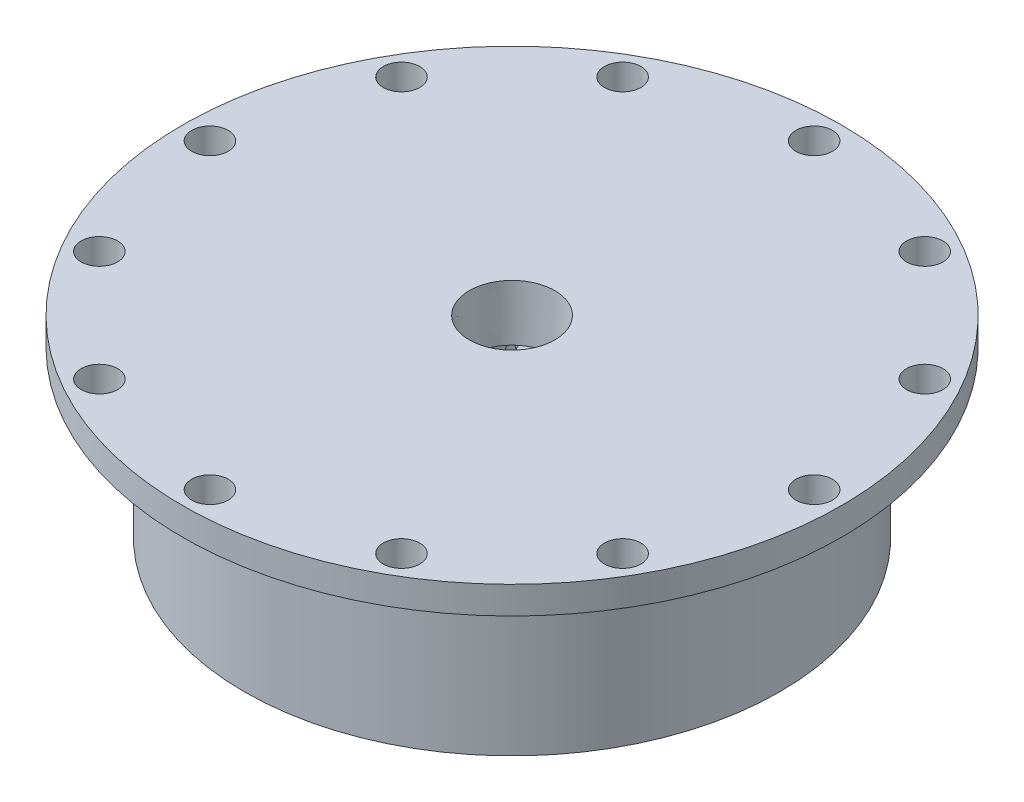
SolidWorks part; units mm, degrees
note: '?' marks a value the reader was unsure of.
ref_plane "Front Plane" through (0, 0, 0) normal (0, 0, 1) x (1, 0, 0)
ref_plane "Top Plane" through (0, 0, 0) normal (0, 1, 0) x (1, 0, 0)
ref_plane "Right Plane" through (0, 0, 0) normal (1, 0, 0) x (0, 0, -1)
sketch "Sketch1" plane through (0, 0, 0) normal (0, 0, 1) x (1, 0, 0)
  line L0 (0, 0) -> (-76.2, 0)
  line L1 (-76.2, 0) -> (-76.2, -6.35)
  line L2 (-76.2, -6.35) -> (-61.9125, -6.35)
  line L3 (-61.9125, -6.35) -> (-61.9125, -44.45)
  line L4 (-61.9125, -44.45) -> (-60.325, -44.45)
  line L5 (-46.0375, -34.925) -> (-46.0375, -50.8)
  line L6 (-46.0375, -50.8) -> (0, -50.8)
  line L7 (0, -50.8) -> (0, 0)
  line L8 (-46.0375, -44.45) -> (-55.5625, -44.45) construction
  line L9 (-60.325, -44.45) -> (-60.325, -42.418)
  line L10 (-60.325, -42.418) -> (-57.277, -42.418)
  line L11 (-57.277, -42.418) -> (-57.277, -44.45)
  line L12 (-57.277, -44.45) -> (-55.5625, -44.45)
  arc A0 (-55.5625, -44.45) -> (-46.0375, -34.925) centre (-46.0375, -44.45) cw
  dimension "D1" = 6.35
  dimension "D2" = 6.35
  dimension "D3" = 9.525
  dimension "D4" = 46.0375
  dimension "D5" = 38.1
  dimension "D6" = 76.2
  dimension "D7" = 6.35
  dimension "D8" = 3.048
  dimension "D9" = 1.5875
  dimension "D10" = 2.032
revolve "Revolve1" add sketch "Sketch1" angle 360 about L7
ref_axis "Axis2" through (0, 1.1112, 0) along (0, -1, 0)
ref_axis "Axis1" through (-83.82, 0, 0) along (1, 0, 0)?
sketch "Sketch2" plane through (0, 0, 0) normal (0, 0, 1) x (1, 0, 0)
  line L0 (0, -50.8) -> (-4.7625, -50.8)
  line L1 (-46.0375, -50.8) -> (46.0375, -50.8) construction
  line L2 (-4.7625, -49.2125) -> (-4.7625, -46.0375)
  line L3 (-4.7625, -46.0375) -> (-6.35, -44.45)
  line L4 (-6.35, -44.45) -> (-6.35, -31.75)
  line L5 (-6.35, -31.75) -> (0, -31.75)
  line L6 (0, -31.75) -> (0, -50.8)
  line L7 (-5.5562, -49.2125) -> (-5.5562, -46.7423)
  line L8 (-5.5562, -46.7423) -> (-7.1437, -45.1548)
  line L9 (-7.1437, -45.1548) -> (-7.1437, -38.1)
  line L10 (-7.1437, -38.1) -> (-10.3187, -38.1)
  line L11 (-10.3187, -38.1) -> (-10.3187, -43.6563)
  line L12 (-10.3187, -43.6563) -> (-6.35, -47.625)
  line L13 (-6.35, -47.625) -> (-6.35, -50.8)
  line L14 (-6.35, -50.8) -> (-5.5562, -50.8)
  line L15 (-5.5562, -49.2125) -> (-4.7625, -49.2125)
  line L16 (-5.5562, -50.8) -> (-4.7625, -50.8)
  line L17 (-4.7625, -50.8) -> (-4.7625, -49.2125) construction
  line L18 (-5.5562, -50.8) -> (-5.5562, -49.2125) construction
  dimension "D1" = 135
  dimension "D2" = 4.7625
  dimension "D3" = 0.7937
  dimension "D4" = 0.7937
  dimension "D5" = 135
  dimension "D6" = 1.5875
  dimension "D7" = 4.7625
  dimension "D8" = 1.5875
  dimension "D9" = 3.175
  dimension "D10" = 6.35
  dimension "D11" = 19.05
  dimension "D12" = 3.175
  dimension "D13" = 0.7937
revolve "Cut-Revolve1" cut sketch "Sketch2" angle 360 about L6
sketch "Sketch4" plane through (0, 0, 0) normal (0, 0, 1) x (1, 0, 0)
  line L0 (-7.9375, -30.1625) -> (-7.9375, -36.5125)
  line L1 (-7.9375, -36.5125) -> (-14.2875, -30.1625)
  line L2 (-7.9375, -30.1625) -> (-0.7938, -23.0187)
  line L3 (-14.2875, -30.1625) -> (-14.2875, -12.7)
  line L4 (-14.2875, -12.7) -> (-0.7937, -12.7)
  line L5 (-0.7938, -23.0187) -> (-0.7937, -12.7)
  line L7 (-6.35, -44.45) -> (-6.35, -31.75) construction
  line L8 (0, 1.1112) -> (0, -23.3363) construction
  line L10 (-7.1437, -38.1) -> (-10.3187, -38.1) construction
  line L11 (-6.35, -31.75) -> (0, -31.75) construction
  line L12 (-83.82, 0) -> (83.82, 0) construction
  dimension "D1" = 45
  dimension "D2" = 1.5875
  dimension "D3" = 14.2875
  dimension "D4" = 1.5875
  dimension "D5" = 0.7937
  dimension "D6" = 1.5875
  dimension "D7" = 12.7
revolve "Cut-Revolve2" cut sketch "Sketch4" angle 360 about axis through (0, 1.1112, 0) along (0, -1, 0)
pattern_linear "LPattern1" count 2 spacing 31.75 along (1, 0, 0) of "Cut-Revolve1", "Cut-Revolve2"
pattern_circular "CirPattern1" count 6 over 360 about axis through (0, 0, 0) along (0, 1, 0) of "LPattern1"
ref_plane "Plane7" through (0, 0, 0) normal (1, 0, 0) x (0, -1, 0)
sketch "Sketch15" plane through (0, 0, 0) normal (1, 0, 0) x (0, -1, 0)
  line L0 (-1.1112, 0) -> (23.3363, 0) construction
  line L1 (20.8301, 3.3676) -> (24.1977, 0)
  line L2 (24.1977, 0) -> (20.8301, -3.3676)
  arc A0 (20.8301, 3.3676) -> (20.8301, -3.3676) centre (17.4625, 0) ccw
  point P7 (12.7, 0)
  dimension "D1" = 4.7625
  dimension "D2" = 12.7
extrude "Cut-Extrude7" cut sketch "Sketch15" against normal blind 19.05 contours A0 L2 L1
pattern_circular "CirPattern11" count 6 over 360 about axis through (0, 0, 0) along (0, 1, 0) of "Cut-Extrude7"
ref_plane "Plane3" through (0, 0, 0) normal (0, 0, 1) x (0, -1, 0)
sketch "Sketch6" plane through (0, 0, 0) normal (0, 0, 1) x (0, -1, 0)
  line L0 (35.2538, 5.5563) -> (34.6925, 6.1175)
  line L1 (34.6925, 4.995) -> (35.2538, 5.5563)
  line L2 (34.1313, 5.5563) -> (35.2538, 5.5563) construction
  line L3 (34.1313, 5.5563) -> (34.1313, 6.35) construction
  line L4 (34.1313, 5.5563) -> (33.3375, 5.5563) construction
  line L5 (50.8, -4.7625) -> (50.8, 4.7625) construction
  arc A0 (34.6925, 6.1175) -> (34.6925, 4.995) centre (34.1313, 5.5563) ccw
  point P21 (50.8, 0)
  dimension "D2" = 0.7937
  dimension "D1" = 90
  dimension "D3" = 17.4625
  dimension "D4" = 6.35
extrude "Cut-Extrude3" cut sketch "Sketch6" against normal up to surface (5.0577 mm away)
ref_plane "Plane4" through (0, 0, 0) normal (-0.5, 0, 0.866) x (0, -1, 0)
sketch "Sketch7" plane through (0, 0, 0) normal (-0.5, 0, 0.866) x (0, -1, 0)
  line L0 (40.0163, 9.525) -> (39.455, 10.0863)
  line L1 (39.455, 8.9637) -> (40.0163, 9.525)
  line L2 (40.0163, 9.525) -> (38.8938, 9.525) construction
  line L3 (38.8938, 9.525) -> (38.8938, 8.7313) construction
  line L4 (38.8938, 9.525) -> (38.1, 9.525) construction
  line L5 (50.8, -4.7625) -> (50.8, 4.7625) construction
  line L6 (38.8938, 9.525) -> (38.8938, 10.3187) construction
  arc A0 (39.455, 10.0863) -> (39.455, 8.9637) centre (38.8938, 9.525) ccw
  point P6 (50.8, 0)
  dimension "D2" = 0.7937
  dimension "D1" = 90
  dimension "D3" = 10.3187
  dimension "D4" = 12.7
extrude "Cut-Extrude4" cut sketch "Sketch7" against normal blind 19.05
pattern_circular "CirPattern3" count 3 over 360 about axis through (0, 0, 0) along (0, 1, 0) of "Cut-Extrude3", "Cut-Extrude4"
ref_axis "Axis3" through (31.75, -44.45, 0) along (0, 1, 0)?
ref_plane "Plane5" through (0, 0, 0) normal (0, 0, 1) x (0, 1, 0)
sketch "Sketch8" plane through (0, 0, 0) normal (0, 0, 1) x (0, 1, 0)
  line L0 (-35.2538, -37.3062) -> (-34.6925, -37.8675)
  line L1 (-34.6925, -36.745) -> (-35.2538, -37.3062)
  line L2 (-34.1313, -37.3062) -> (-35.2538, -37.3062) construction
  line L3 (-34.1313, -37.3062) -> (-34.1313, -38.1) construction
  line L4 (-34.1313, -37.3062) -> (-33.3375, -37.3063) construction
  line L5 (-50.8, -26.9875) -> (-50.8, -36.5125) construction
  arc A0 (-34.6925, -37.8675) -> (-34.6925, -36.745) centre (-34.1313, -37.3062) ccw
  point P14 (-50.8, -31.75)
  dimension "D2" = 0.7937
  dimension "D1" = 90
  dimension "D3" = 6.35
  dimension "D4" = 17.4625
extrude "Cut-Extrude5" cut sketch "Sketch8" against normal blind 7.62
ref_plane "Plane6" through (23.8125, 0, -13.7482) normal (-0.866, 0, 0.5) x (0, 1, 0)
sketch "Sketch9" plane through (23.8125, 0, -13.7482) normal (-0.866, 0, 0.5) x (0, 1, 0)
  line L0 (-40.0163, -25.4) -> (-39.455, -25.9613)
  line L1 (-39.455, -24.8387) -> (-40.0163, -25.4)
  line L2 (-40.0163, -25.4) -> (-38.8938, -25.4) construction
  line L4 (-38.8938, -25.4) -> (-38.1, -25.4) construction
  line L5 (-50.8, -11.1125) -> (-50.8, -20.6375) construction
  line L6 (-38.8938, -25.4) -> (-38.8938, -26.1938) construction
  arc A0 (-39.455, -25.9613) -> (-39.455, -24.8387) centre (-38.8938, -25.4) ccw
  point P6 (-50.8, -15.875)
  dimension "D2" = 0.7937
  dimension "D1" = 90
  dimension "D3" = 10.3187
  dimension "D4" = 12.7
extrude "Cut-Extrude6" cut sketch "Sketch9" against normal blind 15.24
pattern_circular "CirPattern4" count 3 over 360 about axis through (31.75, 0, 0) along (0, 1, 0) of "Cut-Extrude5", "Cut-Extrude6"
pattern_circular "CirPattern9" count 6 over 360 about axis through (0, 0, 0) along (0, 1, 0) of "CirPattern4", "Cut-Extrude5", "Cut-Extrude6"
ref_plane "Plane2" through (-39.8696, 0, 23.0187) normal (-0.866, 0, 0.5) x (0, -1, 0)
sketch "Sketch5" plane through (-39.8696, 0, 23.0187) normal (-0.866, 0, 0.5) x (0, -1, 0)
  line L0 (42.2049, -2.2451) -> (44.45, 0)
  line L1 (44.45, 0) -> (42.2049, 2.2451)
  line L2 (39.9599, 0) -> (44.45, 0) construction
  line L3 (36.7849, 0) -> (39.9599, 0) construction
  line L4 (50.8, -46.0375) -> (50.8, 46.0375) construction
  arc A0 (42.2049, -2.2451) -> (42.2049, 2.2451) centre (39.9599, 0) cw
  dimension "D2" = 3.175
  dimension "D1" = 90
  dimension "D3" = 6.35
extrude "Cut-Extrude2" cut sketch "Sketch5" against normal blind 28.575
pattern_circular "CirPattern2" count 6 over 360 about axis through (0, 0, 0) along (0, 1, 0) of "Cut-Extrude2"
hole_wizard "1/2 NPT Tapped Hole1" positions "Sketch10" profile "Sketch11" size "1/2" standard "ANSI Inch"
sketch "Sketch10" plane through (0, 0, 0) normal (0, 1, 0) x (1, 0, 0)
  point P0 (0, 0)
sketch "Sketch11" plane through (0, 0, 0) normal (1, 0, 0) x (0, 0, 1)
  line L0 (0, 0) -> (0, 27.9705)
  line L1 (8.9281, 22.606) -> (0, 27.9705)
  line L2 (-8.9281, 22.606) -> (0, 27.9705) construction
  line L3 (8.9281, 22.606) -> (8.9281, 13.462)
  line L4 (8.9281, 13.462) -> (9.4797, 13.462)
  line L5 (9.4797, 13.462) -> (9.8828, 0)
  line L6 (-9.4797, 13.462) -> (-9.8828, 0) construction
  line L7 (9.8828, 0) -> (0, 0)
  line L8 (0, -6.35) -> (0, 107.95) construction
  line L11 (-8.9281, 13.462) -> (-9.4797, 13.462) construction
  dimension "Tap Drill Dia." = 17.8562
  dimension "Tap Drill Depth" = 22.606
  dimension "Thread Dia." = 19.7656
  dimension "Thread Angle" = 3.43
  dimension "Thread Depth" = 13.462
  dimension "Drill Angle" = 118
cosmetic thread "Hole Thread1" parameters "D1"=13.462, "D2"=21.3288
hole_wizard "5/16 Clearance Hole1" positions "Sketch12" profile "Sketch14" hole size "5/16" standard "ANSI Inch" end condition through all
sketch "Sketch12" plane through (0, 0, 0) normal (0, 1, 0) x (1, 0, 0)
  line L0 (-83.82, 0) -> (83.82, 0) construction
  point P0 (69.85, 0)
  dimension "D1" = 69.85
sketch "Sketch14" plane through (69.85, 0, 0) normal (1, 0, 0) x (0, 0, 1)
  line L0 (0, 0) -> (0, 50.8)
  line L1 (0, 50.8) -> (4.2164, 50.8)
  line L2 (4.2164, 50.8) -> (4.2164, 0)
  line L5 (4.2164, 0) -> (0, 0)
  line L11 (0, -6.35) -> (0, 107.95) construction
  dimension "Thru Hole Dia." = 8.4328
  dimension "Thru Hole Depth" = 50.8
pattern_circular "CirPattern10" count 12 over 360 about axis through (0, 0, 0) along (0, 1, 0) of "5/16 Clearance Hole1"
sketch "Sketch16" plane through (0, -50.8, 0) normal (0, -1, 0) x (1, 0, 0)
  line L0 (-45.5051, 1.4897) -> (-46.0129, 1.5063)
  line L1 (-45.5051, -1.4897) -> (-46.0129, -1.5063)
  line L2 (0, 0) -> (-45.5051, 1.4897) construction
  line L3 (-45.5051, -1.4897) -> (0, 0) construction
  line L4 (-46.0375, 0) -> (0, 0) construction
  arc A0 (-46.0129, 1.5063) -> (-46.0129, -1.5063) centre (0, 0) ccw
  circle A1 centre (0, 0) radius 46.0375 construction
  arc A2 (-45.5051, -1.4897) -> (-45.5051, 1.4897) centre (0, 0) cw
  dimension "D2" = 0.508
  dimension "D1" = 3.75
extrude "Cut-Extrude8" cut sketch "Sketch16" against normal offset from surface (7.9375 mm away) 1.5875 up to face at (0, -44.45, -60.325) offset beyond the face yes
pattern_circular "CirPattern12" count 6 over 360 about axis through (0, 0, 0) along (0, 1, 0) of "Cut-Extrude8"
